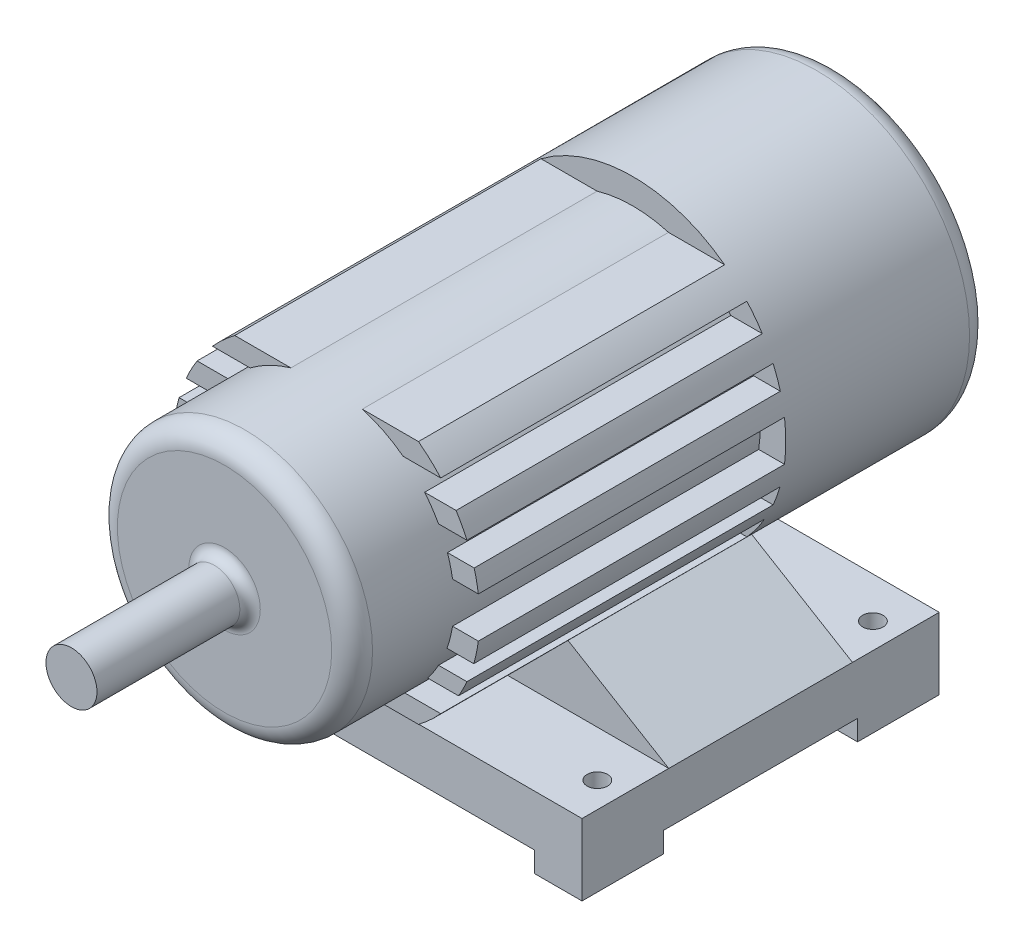
SolidWorks part; units mm, degrees
ref_plane "Front Plane" through (0, 0, 0) normal (0, 0, 1) x (1, 0, 0)
ref_plane "Top Plane" through (0, 0, 0) normal (0, 1, 0) x (1, 0, 0)
ref_plane "Right Plane" through (0, 0, 0) normal (1, 0, 0) x (0, 0, -1)
sketch "Sketch1" plane through (0, 0, 0) normal (0, 0, 1) x (1, 0, 0)
  circle A0 centre (0, 0) radius 150
  dimension "D1" = 300
extrude "Boss-Extrude1" add sketch "Sketch1" along normal blind 200
sketch "Sketch7" plane through (0, 0, 200) normal (0, 0, 1) x (1, 0, 0)
  line L0 (0, 0) -> (0, 100) construction
  line L1 (-90, 120) -> (90, 120)
  line L3 (-111.8034, 100) -> (111.8034, 100)
  line L4 (-126.8858, 80) -> (126.8858, 80)
  line L5 (-137.4773, 60) -> (137.4773, 60)
  line L6 (144.1634, -41.4356) -> (-144.1634, -41.4356)
  line L7 (111.8034, -100) -> (-111.8034, -100)
  line L8 (148.6607, -20) -> (-148.6607, -20)
  line L9 (90, -120) -> (-90, -120)
  line L10 (144.5683, 40) -> (-144.5683, 40)
  line L11 (148.6607, 20) -> (-148.6607, 20)
  line L12 (137.4773, -60) -> (-137.4773, -60)
  line L13 (129.2326, -76.1507) -> (-129.2326, -76.1507)
  arc A0 (-90, 120) -> (-111.8034, 100) centre (0, 0) ccw
  circle A1 centre (0, 0) radius 150 construction
  arc A2 (111.8034, 100) -> (90, 120) centre (0, 0) ccw
  arc A3 (-126.8858, 80) -> (-137.4773, 60) centre (0, 0) ccw
  arc A4 (137.4773, 60) -> (126.8858, 80) centre (0, 0) ccw
  arc A5 (-144.5683, 40) -> (-148.6607, 20) centre (0, 0) ccw
  arc A6 (148.6607, 20) -> (144.5683, 40) centre (0, 0) ccw
  arc A7 (-148.6607, -20) -> (-144.1634, -41.4356) centre (0, 0) ccw
  arc A8 (90, -120) -> (111.8034, -100) centre (0, 0) ccw
  arc A9 (129.2326, -76.1507) -> (137.4773, -60) centre (0, 0) ccw
  arc A10 (-111.8034, -100) -> (-90, -120) centre (0, 0) ccw
  arc A11 (-137.4773, -60) -> (-129.2326, -76.1507) centre (0, 0) ccw
  arc A12 (144.1634, -41.4356) -> (148.6607, -20) centre (0, 0) ccw
  dimension "D1" = 20
  dimension "D2" = 100
  dimension "D3" = 20
  dimension "D4" = 20
  dimension "D5" = 21.4356
  dimension "D6" = 20
  dimension "D7" = 16.1507
  dimension "D8" = 100
  dimension "D9" = 60
  dimension "D10" = 20
  dimension "D11" = 60
  dimension "D12" = 20
extrude "Boss-Extrude11" add sketch "Sketch7" along normal blind 300
sketch "Sketch12" plane through (0, 0, 500) normal (0, 0, 1) x (1, 0, 0)
  circle A0 centre (0, 0) radius 125
  dimension "D1" = 250
extrude "Boss-Extrude14" add sketch "Sketch12" along normal blind 400 from surface separate body starting at face at (0, 0, 200)
ref_plane "Plane4" through (0, -220, 0) normal (0, -1, 0) x (-1, 0, 0)
sketch "Sketch13" plane through (0, -220, 0) normal (0, -1, 0) x (-1, 0, 0)
  line L0 (0, -449.7357) -> (0, 0) construction
  line L1 (-200, -99.7357) -> (200, -99.7357)
  line L2 (-200, -99.7357) -> (-200, -449.7357)
  line L3 (-200, -449.7357) -> (200, -449.7357)
  line L4 (200, -99.7357) -> (200, -449.7357)
  line L5 (150, 0) -> (-150, 0) construction
  line L6 (200, -274.7357) -> (-200, -274.7357) construction
  line L7 (200, -179.7357) -> (150, -179.7357)
  line L8 (-153.3221, -99.7357) -> (-153.3221, -179.7357)
  line L9 (-153.3221, -179.7357) -> (-200, -179.7357)
  line L10 (150, -179.7357) -> (150, -99.7357)
  line L20 (-153.3221, -369.7357) -> (-200, -369.7357)
  line L21 (-153.3221, -449.7357) -> (-153.3221, -369.7357)
  line L25 (200, -369.7357) -> (150, -369.7357)
  line L26 (150, -369.7357) -> (150, -449.7357)
  circle A8 centre (-175, -139.7357) radius 10
  circle A9 centre (-175, -409.7357) radius 10
  circle A10 centre (175, -409.7357) radius 10
  circle A11 centre (175, -139.7357) radius 10
  point P19 (0, 0)
  point P20 (0, 0)
  point P21 (0, 0)
  point P24 (0, 0)
  point P26 (-178.2183, -141.9624)
  point P28 (-175, -139.7357)
  dimension "D7" = 20
  dimension "D9" = 40
  dimension "D1" = 99.7357
  dimension "D2" = 350
  dimension "D3" = 400
  dimension "D4" = 80
  dimension "D5" = 46.6779
  dimension "D6" = 50
  dimension "D8" = 25
extrude "Boss-Extrude15" add sketch "Sketch13" against normal blind 50 separate body contours L26 L25 L4 L7 L10 L1 L8 L9 L2 L20 L21 L3 | L9 L8 L1 L2 | L3 L21 L20 L2 | L25 L26 L3 L4 | L10 L7 L4 L1 region at (176.661, -220, 100.6619) region at (0.6473, -220, 274.7357) region at (-175, -220, 100.6791) region at (176.661, -220, 370.6619) region at (-199.0566, -220, 409.7357)
cosmetic thread "Cosmetic Thread1" parameters "D2"=22
cosmetic thread "Cosmetic Thread2" parameters "D2"=22
cosmetic thread "Cosmetic Thread3" parameters "D2"=22
cosmetic thread "Cosmetic Thread4" parameters "D2"=22
extrude "Boss-Extrude16" add sketch "Sketch13<3>" along normal blind 20 contours L3 L21 L20 L2 | L9 L8 L1 L2 | L25 L26 L3 L4 | L10 L7 L4 L1 region at (176.661, -220, 100.6619) region at (-175, -220, 100.6791) region at (176.661, -220, 370.6619) region at (-199.0566, -220, 409.7357)
sketch "Sketch13<3>" plane through (0, -220, 0) normal (0, -1, 0) x (-1, 0, 0) same geometry as "Sketch13"
ref_plane "Plane5" through (0, 0, 274.7357) normal (0, 0, 1) x (1, 0, 0)
sketch "Sketch14" plane through (0, 0, 274.7357) normal (0, 0, 1) x (1, 0, 0)
  line L0 (-200, -170) -> (200, -170)
  line L1 (200, -170) -> (100, -110)
  line L2 (100, -110) -> (-100, -110)
  line L3 (-100, -110) -> (-200, -170)
  line L4 (200, -170) -> (-200, -170) construction
  dimension "D1" = 60
  dimension "D2" = 200
extrude "Boss-Extrude17" add sketch "Sketch14" along normal mid plane 180
sketch "Sketch16" plane through (0, 0, 600) normal (0, 0, 1) x (1, 0, 0)
  circle A0 centre (0, 0) radius 25
  dimension "D1" = 50
extrude "Boss-Extrude18" add sketch "Sketch16" along normal blind 150
fillet "Fillet2" radius 10 1 edges at (25, 0, 600)
fillet "Fillet3" radius 20 2 edges at (150, 0, 0) (125, 0, 600)
